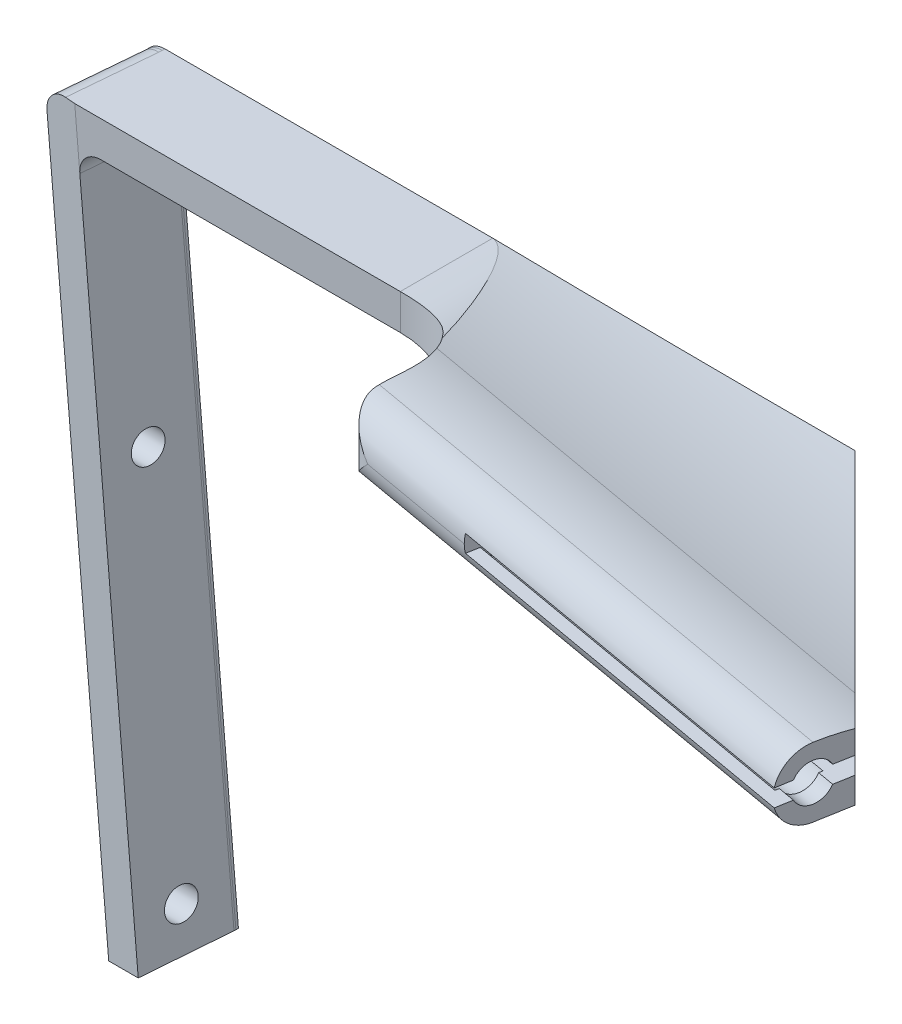
SolidWorks part; units mm, degrees
ref_plane "Front Plane" through (0, 0, 0) normal (0, 0, 1) x (1, 0, 0)
ref_plane "Top Plane" through (0, 0, 0) normal (0, 1, 0) x (1, 0, 0)
ref_plane "Right Plane" through (0, 0, 0) normal (1, 0, 0) x (0, 0, -1)
sketch "Sketch1" plane through (0, 0, 0) normal (0, 0, 1) x (1, 0, 0)
  line L0 (0, 0) -> (76.2, 0)
  line L1 (76.2, 0) -> (76.2, -5.08)
  line L2 (76.2, -5.08) -> (2.8536, -5.08)
  line L3 (2.8536, -5.08) -> (7.2811, -55.6867)
  line L4 (7.2811, -55.6867) -> (4.8903, -55.8959)
  line L5 (4.8903, -55.8959) -> (0, 0)
  dimension "D1" = 5.08
  dimension "length1" = 76.2
  dimension "D3" = 2.4
  dimension "D4" = 85
  dimension "D5" = 50.8
extrude "OverallGeometry-Boss-Extrude1" add sketch "Sketch1" along normal blind 0.254
sketch "Sketch2" plane through (4.8903, -55.8959, 0) normal (0.0872, -0.9962, 0) x (0.9962, 0.0872, 0)
  line L0 (2.4, 0.254) -> (1.8283, 6.7882)
  line L1 (1.8283, 6.7882) -> (-0.5534, 6.5798)
  line L2 (-0.5534, 6.5798) -> (0, 0.254)
  line L3 (0, 0.254) -> (2.4, 0.254) construction
  line L4 (0, 0.254) -> (2.4, 0.254)
  line L5 (2.4, 0.254) -> (75.4673, 0.254) construction
  dimension "D1" = 6.35
  dimension "D2" = 95
extrude "CameraPitch-Boss-Extrude2" add sketch "Sketch2" against normal up to vertex (56.1094 mm away) up to point (0, 0, 0.254)
sketch "Sketch4" plane through (0, -5.08, 0) normal (0, -1, 0) x (1, 0, 0)
  line L0 (76.2, 0.254) -> (71.7893, 25.2681)
  line L1 (-1.9886, 6.7882) -> (33.5714, 6.7882)
  line L2 (2.8536, 0.254) -> (76.2, 0.254) construction
  line L3 (7.2811, 0.254) -> (6.7116, 6.7882) construction
  line L7 (-1.4191, 0) -> (-1.4191, 0.254)
  line L8 (-1.4191, 0.254) -> (-1.9886, 6.7882)
  line L10 (-1.4191, 0) -> (76.2, 0)
  line L11 (76.2, 0) -> (76.2, 0.254)
  line L12 (33.5714, 6.7882) -> (33.5714, 18.5293)
  line L13 (33.5714, 18.5293) -> (71.7893, 25.2681)
  dimension "D1" = 80
  dimension "D2" = 25.4
  dimension "D3" = 35.56
  dimension "D4" = 3.81
extrude "Boss-Extrude3" add sketch "Sketch4" against normal up to surface (5.08 mm away) up to face at (30.9618, 0, 0.1524)
sketch "Sketch3" plane through (2.3947, 0.2095, 0.2103) normal (0.9924, 0.0868, 0.0872) x (0.1097, -0.3046, -0.9461)
  line L0 (14.3063, -54.3631) -> (13.3284, -51.3959) construction
  line L1 (17.5204, -53.3038) -> (11.2908, -55.3568) construction
  line L2 (13.3284, -51.3959) -> (4.5833, -24.8597) construction
  line L4 (-4.6251, -7.0618) -> (11.2908, -55.3568) construction
  circle A0 centre (4.5833, -24.8597) radius 1.143
  circle A1 centre (13.3284, -51.3959) radius 1.143
  dimension "D4" = 2.286
  dimension "D1" = 27.94
  dimension "D2" = 3.1242
  dimension "D3" = 3.175
extrude "Cut-Extrude1" cut sketch "Sketch3" against normal through all
sketch "Sketch5" plane through (73.9457, 0, 13.0386) normal (0.9848, 0, 0.1736) x (0.1736, 0, -0.9848)
  line L0 (-12.4182, -2.54) -> (-9.8782, -2.54) construction
  line L1 (-12.4182, 0) -> (-12.4182, -5.08) construction
  line L2 (-12.4182, -1.905) -> (-11.4022, -1.905)
  line L3 (-12.4182, -3.175) -> (-11.4022, -3.175)
  line L4 (-12.4182, -3.175) -> (-12.4182, -1.905)
  line L5 (-8.3542, -1.905) -> (-4.5442, -1.905)
  line L6 (-4.5442, -1.905) -> (-4.5442, -3.175)
  line L7 (-4.5442, -3.175) -> (-8.3542, -3.175)
  arc A0 (-11.4022, -3.175) -> (-8.3542, -3.175) centre (-9.8782, -2.54) ccw
  arc A1 (-8.3542, -1.905) -> (-11.4022, -1.905) centre (-9.8782, -2.54) ccw
  dimension "D1" = 3.302
  dimension "D2" = 2.54
  dimension "D3" = 1.27
  dimension "D4" = 3.81
extrude "Cut-Extrude2" cut sketch "Sketch5" against normal blind 27.94
sketch "Sketch6" plane through (73.9457, 0, 13.0386) normal (0.9848, 0, 0.1736) x (0.1736, 0, -0.9848)
  line L0 (-11.4022, -1.905) -> (-11.1225, -1.905)
  line L1 (-8.3542, -1.905) -> (-8.6338, -1.905)
  line L2 (-8.3542, -3.175) -> (-8.6338, -3.175)
  line L3 (-11.4022, -3.175) -> (-11.1225, -3.175)
  line L4 (-12.4182, -3.175) -> (-11.4022, -3.175) construction
  line L5 (-4.5442, -1.905) -> (-8.3542, -1.905) construction
  arc A0 (-11.4022, -3.175) -> (-8.3542, -3.175) centre (-9.8782, -2.54) ccw
  arc A2 (-11.1225, -3.175) -> (-8.6338, -3.175) centre (-9.8782, -2.54) ccw
  arc A3 (-8.6338, -1.905) -> (-11.1225, -1.905) centre (-9.8782, -2.54) ccw
  arc A4 (-8.3542, -1.905) -> (-11.4022, -1.905) centre (-9.8782, -2.54) ccw
  dimension "D1" = 0.254
extrude "Boss-Extrude4" add sketch "Sketch6" against normal blind 1.27
sketch "Sketch8" plane through (4.8903, -55.8959, 0) normal (0.0872, -0.9962, 0) x (0.9962, 0.0872, 0)
  line L0 (1.8283, 6.7882) -> (-0.5534, 6.5798)
  line L1 (-0.5534, 6.5798) -> (0, 0.254)
  line L2 (0, 0.254) -> (0, 0)
  line L3 (0, 0) -> (-7.3483, 0)
  line L4 (-7.3483, 0) -> (-7.3483, 6.7882)
  line L5 (-7.3483, 6.7882) -> (1.8283, 6.7882)
extrude "Cut-Extrude4" cut sketch "Sketch8" against normal through all
sketch "Sketch9" plane through (0, 0, 0) normal (0, 1, 0) x (1, 0, 0)
  line L0 (72.6935, -20.1402) -> (52.5533, 0)
  line L1 (71.7893, -25.2681) -> (76.2, -0.254) construction
  line L2 (76.2, 0) -> (0, 0) construction
  line L3 (52.5533, 0) -> (76.2, 0)
  line L4 (76.2, 0) -> (76.2, -20.1402)
  line L5 (76.2, -20.1402) -> (72.6935, -20.1402)
  dimension "D1" = 45
  dimension "D2" = 5.207
extrude "Cut-Extrude5" cut sketch "Sketch9" against normal through all
fillet "Fillet1" radius 2.54 1 edges at (33.5714, -2.54, 18.5293)
fillet "Fillet2" radius 7.62 1 edges at (33.5714, -2.54, 6.7882)
sketch "Sketch10" plane through (73.9457, 0, 13.0386) normal (0.9848, 0, 0.1736) x (0.1736, 0, -0.9848)
  line L0 (9.1258, 0) -> (9.1258, 48.4539) construction
  circle A0 centre (9.1258, 48.4539) radius 51.1339
  point P4 (9.1258, -2.68)
  dimension "D1" = 2.4
extrude "Cut-Extrude6" cut sketch "Sketch10" against normal through all
fillet "Fillet3" radius 2.54 2 edges at (53.7298, -5.08, 22.0837) (53.7298, 0, 22.0837) tangent propagation no
fillet "Fillet4" radius 17.78 1 edges at (53.0863, 0, 16.6829)
sketch "Sketch13" plane through (0, 0, 6.7882) normal (0, 0, 1) x (1, 0, 0)
  line L0 (-24.8486, 10.2291) -> (25.9514, 10.2291) construction
  line L1 (-24.8486, 22.9291) -> (25.9514, 22.9291)
  line L2 (-24.8486, -2.4709) -> (25.9514, -2.4709)
  line L3 (25.9514, -5.08) -> (25.9514, -1.4148) construction
  arc A0 (-24.8486, 22.9291) -> (-24.8486, -2.4709) centre (-24.8486, 10.2291) ccw
  arc A1 (25.9514, -2.4709) -> (25.9514, 22.9291) centre (25.9514, 10.2291) ccw
  ellipse E0 centre (52.5533, 48.4539) end of major axis (347.0218, 48.4539) minor radius 51.1339 (0.1631, -1.8642) -> (52.5533, -2.68) ccw construction
  point P2 (0.5514, 10.2291)
  dimension "D2" = 12.7
  dimension "D1" = 50.8
extrude "Cut-Extrude8" cut sketch "Sketch13" against normal through all and the other way through all
fillet "Fillet14" radius 1.524 1 edges
fillet "Fillet15" radius 1.524 3 edges at (2.8522, -5.08, 0.2539)
fillet "Fillet16" radius 1.524 1 edges at (2.5532, -29.1834, 0.254)
fillet "Fillet17" radius 1.524 3 edges at (0.2162, -2.4709, 0.0937) (0.2147, -2.4709, 0.2539) (-0.0645, -2.4709, 3.4501)
